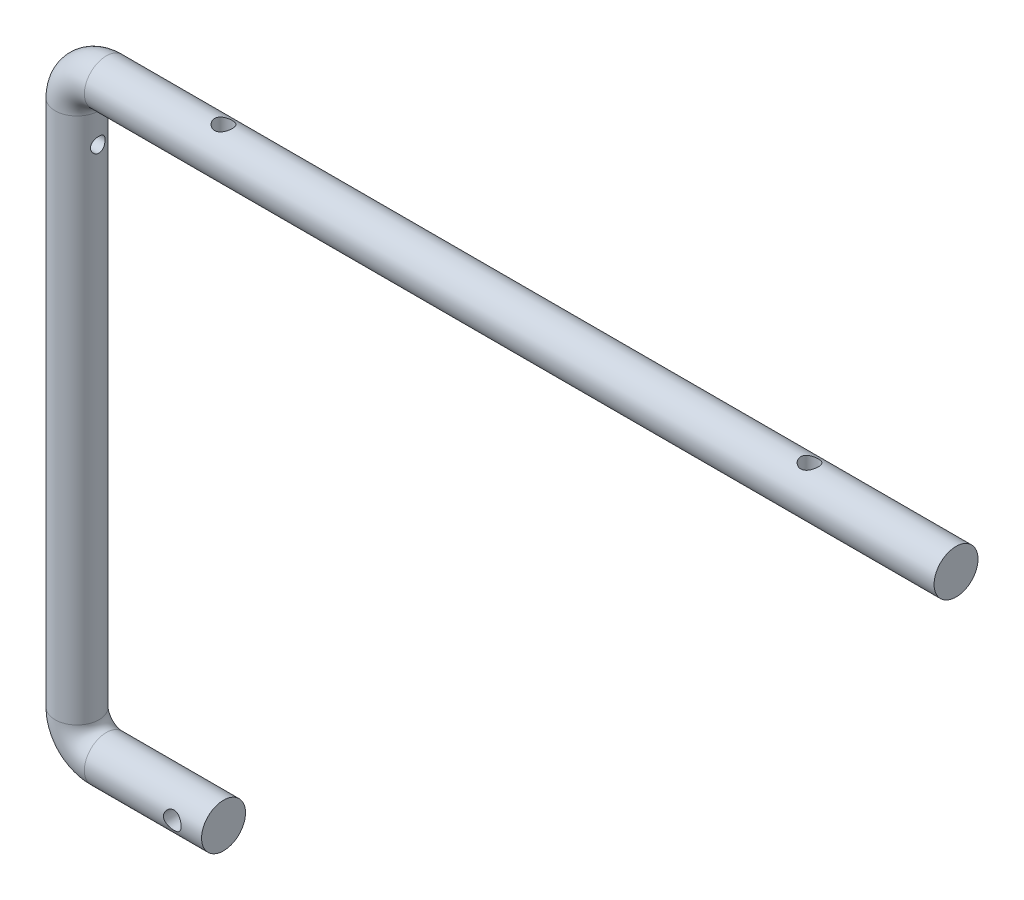
SolidWorks part; units mm, degrees
ref_plane "前视基准面" through (0, 0, 0) normal (0, 0, 1) x (1, 0, 0)
ref_plane "上视基准面" through (0, 0, 0) normal (0, 1, 0) x (1, 0, 0)
ref_plane "右视基准面" through (0, 0, 0) normal (1, 0, 0) x (0, 0, -1)
sketch "草图1" plane through (0, 0, 0) normal (0, 0, 1) x (1, 0, 0)
  line L0 (0, 0) -> (-40, 0)
  line L1 (-50, 10) -> (-50, 190)
  line L2 (-40, 200) -> (250, 200)
  arc A0 (-50, 190) -> (-40, 200) centre (-40, 190) cw
  arc A1 (-40, 0) -> (-50, 10) centre (-40, 10) cw
  point P7 (-50, 200)
  point P10 (-50, 0)
  dimension "D4" = 10
  dimension "D1" = 50
  dimension "D2" = 200
  dimension "D3" = 300
sketch "草图2" plane through (0, 0, 0) normal (1, 0, 0) x (0, 0, -1)
  circle A0 centre (0, 0) radius 7.5
  dimension "D1" = 15
sweep "扫描1" add profiles "草图2" path "草图1"
sketch "草图3" plane through (0, 0, 0) normal (0, 0, 1) x (1, 0, 0)
  line L0 (0, 0) -> (-10, 0) construction
  circle A0 centre (-10, 0) radius 3
  dimension "D2" = 6
  dimension "D1" = 10
extrude "切除-拉伸1" cut sketch "草图3" against normal blind 10 and the other way blind 10
ref_plane "基准面1" through (0, 50, 0) normal (0, 1, 0) x (1, 0, 0)
sketch "草图4" plane through (0, 50, 0) normal (0, 1, 0) x (1, 0, 0)
  line L0 (250, 0) -> (200, 0) construction
  line L1 (250, -7.5) -> (250, 7.5) construction
  line L2 (200, 0) -> (0, 0) construction
  circle A0 centre (200, 0) radius 3
  circle A1 centre (0, 0) radius 3
  dimension "D3" = 6
  dimension "D4" = 6
  dimension "D1" = 50
  dimension "D2" = 200
extrude "切除-拉伸2" cut sketch "草图4" along normal blind 175
sketch "草图5" plane through (0, 0, 0) normal (1, 0, 0) x (0, 0, -1)
  circle A0 centre (0, 180) radius 2.5
extrude "切除-拉伸3" cut sketch "草图5" against normal through all
